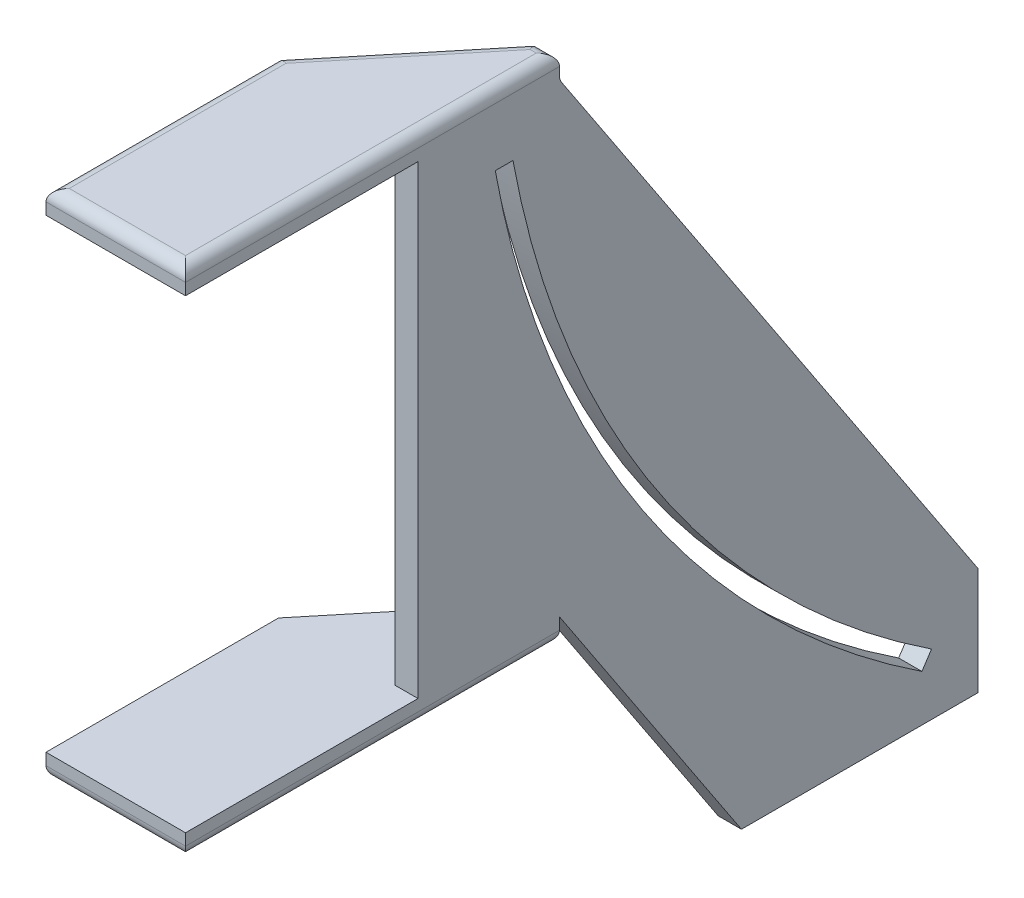
SolidWorks part; units mm, degrees
ref_plane "Front Plane" through (0, 0, 0) normal (0, 0, 1) x (1, 0, 0)
ref_plane "Top Plane" through (0, 0, 0) normal (0, 1, 0) x (1, 0, 0)
ref_plane "Right Plane" through (0, 0, 0) normal (1, 0, 0) x (0, 0, -1)
sketch "Sketch1" plane through (0, 0, 0) normal (1, 0, 0) x (0, 0, -1)
  line L0 (-132.3245, -23.876) -> (-129.9041, -23.876)
  line L1 (-74.0657, -112.2234) -> (-72.7541, -110.236)
  line L2 (-123.5541, -17.526) -> (-66.4041, -103.886)
  line L3 (-142.875, -17.526) -> (-123.5541, -17.526)
  line L4 (-142.875, -17.526) -> (-142.875, -81.026)
  line L5 (-98.7065, -118.5734) -> (-66.4041, -118.5734)
  line L6 (-66.4041, -103.886) -> (-66.4041, -118.5734)
  line L7 (-142.875, -81.026) -> (-123.5541, -81.026)
  line L8 (-123.5541, -81.026) -> (-98.7065, -118.5734)
  arc A0 (-129.9041, -23.876) -> (-72.7541, -110.236) centre (0, 0) ccw
  arc A1 (-132.3245, -23.876) -> (-74.0657, -112.2234) centre (0, 0) ccw
  point P14 (-131.1143, -23.876)
  dimension "D1" = 132.08
  dimension "D2" = 2.3813
  dimension "D3" = 142.875
  dimension "D4" = 6.35
  dimension "D5" = 6.35
  dimension "D6" = 6.35
  dimension "D7" = 6.35
  dimension "D8" = 6.35
  dimension "D9" = 57.15
  dimension "D10" = 17.526
  dimension "D11" = 0
  dimension "D12" = 63.5
extrude "Boss-Extrude1" add sketch "Sketch1" along normal blind 3.175
sketch "Sketch2" plane through (0, -17.526, 0) normal (0, 1, 0) x (1, 0, 0)
  line L1 (0, -123.5541) -> (3.175, -123.5541)
  line L9 (0, -123.5541) -> (-15.875, -142.875)
  line L10 (3.175, -123.5541) -> (3.175, -174.625)
  line L11 (3.175, -174.625) -> (-15.875, -174.625)
  line L12 (-15.875, -142.875) -> (-15.875, -174.625)
extrude "Boss-Extrude2" add sketch "Sketch2" along normal blind 3.175
fillet "Fillet1" radius 1.5875 6 edges at (1.5875, -14.351, 123.5541) (1.5875, -17.526, 123.5541) (3.175, -14.351, 149.0895) (-6.35, -14.351, 174.625) (-15.875, -14.351, 158.75) (-7.9375, -14.351, 133.2145)
sketch "Sketch4" plane through (0, -81.026, 0) normal (0, -1, 0) x (1, 0, 0)
  line L0 (3.175, 123.5541) -> (3.175, 174.625)
  line L1 (3.175, 174.625) -> (-15.875, 174.625)
  line L2 (-15.875, 174.625) -> (-15.875, 142.875)
  line L3 (0, 123.5541) -> (-15.875, 142.875) construction
  line L4 (-15.875, 142.875) -> (-15.875, 174.625) construction
  line L5 (-15.875, 142.875) -> (0, 123.5541)
  line L6 (0, 123.5541) -> (3.175, 123.5541)
extrude "Boss-Extrude3" add sketch "Sketch4" along normal blind 3.175
fillet "Fillet2" radius 1.5875 5 edges at (-7.9375, -84.201, 133.2145) (-15.875, -84.201, 158.75) (-6.35, -84.201, 174.625) (3.175, -84.201, 149.0895) (1.5875, -84.201, 123.5541)
